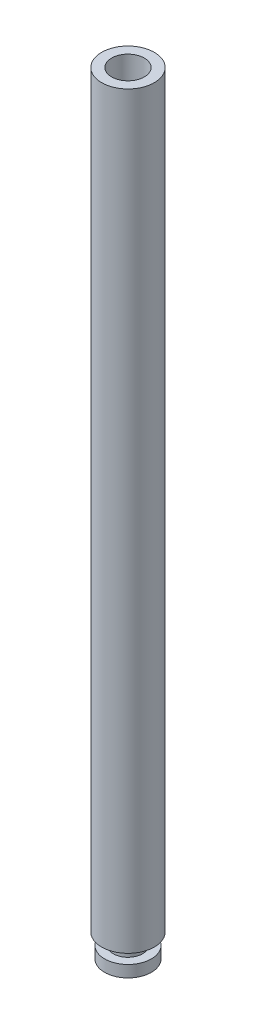
SolidWorks part; units mm, degrees
ref_plane "Front Plane" through (0, 0, 0) normal (0, 0, 1) x (1, 0, 0)
ref_plane "Top Plane" through (0, 0, 0) normal (0, 1, 0) x (1, 0, 0)
ref_plane "Right Plane" through (0, 0, 0) normal (1, 0, 0) x (0, 0, -1)
sketch "Sketch1" plane through (0, 0, 0) normal (0, 1, 0) x (1, 0, 0)
  circle A0 centre (-0.522, 0.5111) radius 1.375
  circle A1 centre (-0.522, 0.5111) radius 2.25
  dimension "D1" = 2.75
  dimension "D2" = 4.5
extrude "Boss-Extrude1" add sketch "Sketch1" along normal blind 64 contours A1
extrude "Boss-Extrude2" add sketch "Sketch1<3>" along normal blind 1 contours A0 region at (-0.522, 0, -0.5111)
sketch "Sketch1<3>" plane through (0, 0, 0) normal (0, 1, 0) x (1, 0, 0) same geometry as "Sketch1"
sketch "Sketch5" plane through (0, 0, 0) normal (0, -1, 0) x (1, 0, 0)
  circle A3 centre (-0.522, -0.5111) radius 1.25
  dimension "D1" = 2.5
extrude "Boss-Extrude3" add sketch "Sketch5" along normal blind 1 contours A3
sketch "Sketch6" plane through (0, -1, 0) normal (0, -1, 0) x (1, 0, 0)
  circle A0 centre (-0.522, -0.5111) radius 2
  dimension "D1" = 4
extrude "Boss-Extrude4" add sketch "Sketch6" along normal blind 1
sketch "Sketch8" plane through (0, -2, 0) normal (0, -1, 0) x (-1, 0, 0)
  circle A0 centre (0.522, 0.5111) radius 1.5
  dimension "D1" = 3
sketch "Sketch11" plane through (0, 64, 0) normal (0, 1, 0) x (1, 0, 0)
  text T0 "VIII" font "Century Gothic" height in points 5
sketch "Sketch12" plane through (0, 64, 0) normal (0, 1, 0) x (1, 0, 0)
  circle A0 centre (-0.522, 0.5111) radius 1.4
  dimension "D1" = 2.8
extrude "Cut-Extrude1" cut sketch "Sketch12" against normal blind 7.5
